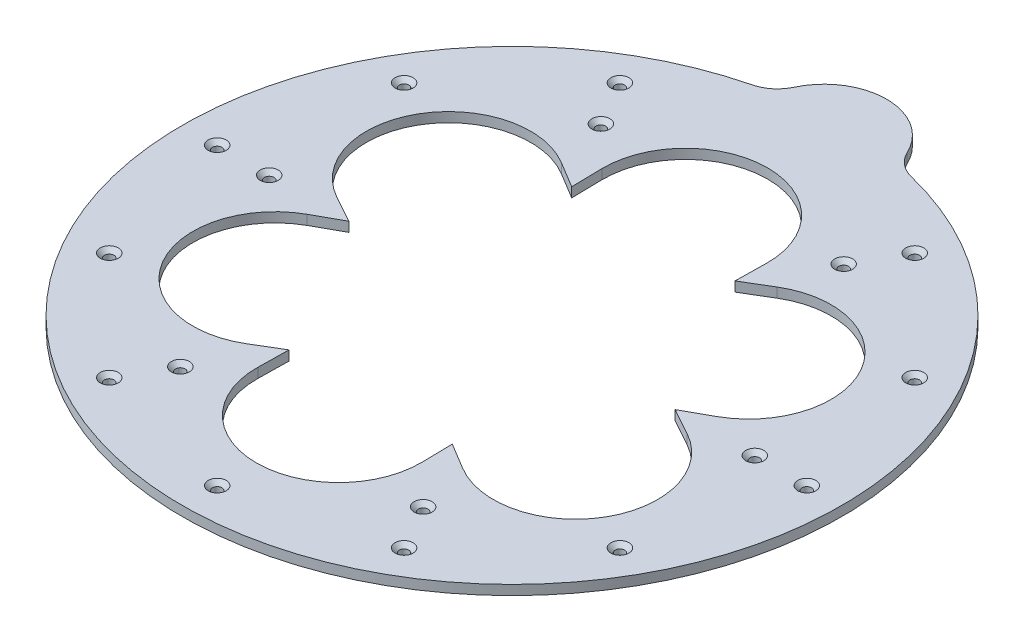
SolidWorks part; units mm, degrees
ref_plane "Front Plane" through (0, 0, 0) normal (0, 0, 1) x (1, 0, 0)
ref_plane "Top Plane" through (0, 0, 0) normal (0, 1, 0) x (1, 0, 0)
ref_plane "Right Plane" through (0, 0, 0) normal (1, 0, 0) x (0, 0, -1)
sketch "Sketch5" plane through (0, 0, 0) normal (0, 1, 0) x (1, 0, 0)
  line L25 (-47.3671, -99.136) -> (-47.0452, -81.4846)
  line L26 (47.0452, -81.4846) -> (47.3671, -99.136)
  line L28 (-47.0452, -81.4846) -> (-62.1707, -90.5891)
  line L31 (-109.5379, -8.5469) -> (-94.0903, 0)
  line L32 (-94.0903, 0) -> (-109.5379, 8.5469)
  line L35 (-62.1707, 90.5891) -> (-47.0452, 81.4846)
  line L36 (-47.0452, 81.4846) -> (-47.3671, 99.136)
  line L39 (47.3671, 99.136) -> (47.0452, 81.4846)
  line L40 (47.0452, 81.4846) -> (62.1707, 90.5891)
  line L43 (109.5379, 8.5469) -> (94.0903, 0)
  line L44 (94.0903, 0) -> (109.5379, -8.5469)
  line L47 (62.1707, -90.5891) -> (47.0452, -81.4846)
  circle A0 centre (0, 0) radius 47.9176 construction
  arc A6 (-45.8766, 184.3783) -> (45.8567, 184.3832) centre (0, 0) ccw
  circle A7 centre (0, 0) radius 29.9227 construction
  arc A14 (32.5786, 195.2947) -> (-32.5996, 195.2912) centre (-0.0097, 180) ccw
  arc A15 (-32.5996, 195.2912) -> (-45.8766, 184.3783) centre (-50.7057, 203.7865) cw
  arc A16 (32.5786, 195.2947) -> (45.8567, 184.3832) centre (50.6837, 203.792) ccw
  arc A19 (-47.3671, -99.136) -> (47.3671, -99.136) centre (0, -100) ccw
  arc A20 (-109.5379, -8.5469) -> (-62.1707, -90.5891) centre (-86.6025, -50) ccw
  arc A22 (-62.1707, 90.5891) -> (-109.5379, 8.5469) centre (-86.6025, 50) ccw
  arc A24 (47.3671, 99.136) -> (-47.3671, 99.136) centre (0, 100) ccw
  arc A26 (109.5379, 8.5469) -> (62.1707, 90.5891) centre (86.6025, 50) ccw
  arc A28 (62.1707, -90.5891) -> (109.5379, -8.5469) centre (86.6025, -50) ccw
  point P1 (0, 0)
  point P2 (0, 0)
  point P8 (0, 0)
  point P10 (0, 0)
  point P39 (-255.3022, 150.011)
  point P40 (139.5, 300)
  point P41 (0, 300)
  point P42 (-124.8076, 150)
  point P43 (-120.3076, 150)
  point P45 (-259.8076, 150)
  point P46 (135, 300)
  point P51 (0, 300)
  point P74 (0, 0)
  point P121 (0, 0)
  dimension "D2" = 20
sketch "Sketch6" plane through (0, 0, 68.1456) normal (0, -1, 0) x (1, 0, 0)
  line L0 (0, -68.1456) -> (-154.7306, -68.1456)
  circle A0 centre (0, -68.1456) radius 32.7528 construction
  circle A1 centre (0, -68.1456) radius 203.9043 construction
extrude "Boss-Extrude3" add sketch "Sketch5" against normal blind 5.6
hole_wizard "CSK for M5 Flat Head Machine Screw1" positions "Sketch8" profile "Sketch7" countersink size "M5" standard "ANSI Metric" end condition through all
sketch "Sketch8" plane through (0, 0, 68.1456) normal (0, -1, 0) x (1, 0, 0)
  line L0 (0, -68.1456) -> (-154.7306, -68.1456) construction
  point P0 (-170, -68.1456)
  dimension "D1" = 0
  dimension "D2" = 170
sketch "Sketch7" plane through (-170, 0, 0) normal (1, 0, 0) x (0, 0, 1)
  line L0 (0, 0) -> (0, 5.6)
  line L1 (0, 5.6) -> (2.75, 5.6)
  line L2 (2.75, 5.6) -> (2.75, 2.45)
  line L3 (2.75, 2.45) -> (5.2, 0)
  line L5 (5.2, 0) -> (0, 0)
  line L6 (-2.75, 2.45) -> (-5.2, 0) construction
  line L11 (0, -6.35) -> (0, 107.95) construction
  dimension "Thru Hole Dia." = 5.5
  dimension "Thru Hole Depth" = 5.6
  dimension "Near C'Sink Dia." = 10.4
  dimension "Near C'Sink Angle" = 90
pattern_circular "CirPattern1" count 12 every 30 about axis through (0, -5.6, 0) along (0, 1, 0) skipping 9 of "CSK for M5 Flat Head Machine Screw1"
hole_wizard "CSK for M5 Flat Head Machine Screw2" positions "Sketch10" profile "Sketch9" countersink size "M5" standard "ANSI Metric" end condition through all
sketch "Sketch10" plane through (0, 0, 68.1456) normal (0, -1, 0) x (1, 0, 0)
  line L0 (0, -68.1456) -> (-154.7306, -68.1456) construction
  point P0 (-140, -68.1456)
  dimension "D1" = 0
  dimension "D2" = 140
sketch "Sketch9" plane through (-140, 0, 0) normal (1, 0, 0) x (0, 0, 1)
  line L0 (0, 0) -> (0, 5.6)
  line L1 (0, 5.6) -> (2.75, 5.6)
  line L2 (2.75, 5.6) -> (2.75, 2.45)
  line L3 (2.75, 2.45) -> (5.2, 0)
  line L5 (5.2, 0) -> (0, 0)
  line L6 (-2.75, 2.45) -> (-5.2, 0) construction
  line L11 (0, -6.35) -> (0, 107.95) construction
  dimension "Thru Hole Dia." = 5.5
  dimension "Thru Hole Depth" = 5.6
  dimension "Near C'Sink Dia." = 10.4
  dimension "Near C'Sink Angle" = 90
pattern_circular "CirPattern2" count 6 over 360 about axis through (0, -5.6, 0) along (0, 1, 0) of "CSK for M5 Flat Head Machine Screw2"
ref_plane "Plane1" [suppressed] through (0, 0, 0) normal (0, 1, 0) x (1, 0, 0)
sketch "Sketch11" [suppressed] plane through (0, 0, 0) normal (0, 1, 0) x (1, 0, 0)
  circle A0 centre (-0.0097, 180) radius 6.35
extrude "Cut-Extrude1" [suppressed] cut sketch "Sketch11" against normal blind 10
sketch "keepThisTemplate" plane through (0, 0, 0) normal (0, 1, 0) x (1, 0, 0)
  line L0 (-86.6025, -4.4286) -> (-67.2981, -15.1094)
  line L1 (-47.1365, -72.7857) -> (-46.7342, -50.7272)
  line L2 (-47.1365, -72.7857) -> (-66.0386, -84.1634)
  line L3 (-105.9069, -15.1094) -> (-86.6025, -4.4286)
  line L4 (-47.1365, 72.7857) -> (-46.7342, 50.7272)
  line L5 (-86.6025, 4.4286) -> (-67.2981, 15.1094)
  line L6 (-86.6025, 4.4286) -> (-105.9069, 15.1094)
  line L7 (-66.0386, 84.1634) -> (-47.1365, 72.7857)
  line L8 (-39.466, -77.2143) -> (-20.564, -65.8366)
  line L9 (39.466, -77.2143) -> (20.564, -65.8366)
  line L10 (39.466, -77.2143) -> (39.8684, -99.2728)
  line L11 (-39.8684, -99.2728) -> (-39.466, -77.2143)
  line L12 (39.466, 77.2143) -> (20.564, 65.8366)
  line L13 (-39.466, 77.2143) -> (-20.564, 65.8366)
  line L14 (-39.466, 77.2143) -> (-39.8684, 99.2728)
  line L15 (39.8684, 99.2728) -> (39.466, 77.2143)
  line L16 (86.6025, 4.4286) -> (67.2981, 15.1094)
  line L17 (47.1365, 72.7857) -> (46.7342, 50.7272)
  line L18 (47.1365, 72.7857) -> (66.0386, 84.1634)
  line L19 (105.9069, 15.1094) -> (86.6025, 4.4286)
  line L20 (47.1365, -72.7857) -> (46.7342, -50.7272)
  line L21 (86.6025, -4.4286) -> (67.2981, -15.1094)
  line L22 (86.6025, -4.4286) -> (105.9069, -15.1094)
  line L23 (66.0386, -84.1634) -> (47.1365, -72.7857)
  line L24 (-46.8891, -72.9286) -> (-24.4318, -59.4109)
  line L25 (-47.3671, -99.136) -> (-46.8891, -72.9286)
  line L26 (46.8891, -72.9286) -> (47.3671, -99.136)
  line L27 (46.8891, -72.9286) -> (24.4318, -59.4109)
  line L28 (-39.7135, -77.0714) -> (-62.1707, -90.5891)
  line L29 (-39.7135, -77.0714) -> (-39.2354, -50.864)
  line L30 (-86.6025, 4.1429) -> (-63.6672, -8.5469)
  line L31 (-109.5379, -8.5469) -> (-86.6025, 4.1429)
  line L32 (-86.6025, -4.1429) -> (-109.5379, 8.5469)
  line L33 (-86.6025, -4.1429) -> (-63.6672, 8.5469)
  line L34 (-39.7135, 77.0714) -> (-39.2354, 50.864)
  line L35 (-62.1707, 90.5891) -> (-39.7135, 77.0714)
  line L36 (-46.8891, 72.9286) -> (-47.3671, 99.136)
  line L37 (-46.8891, 72.9286) -> (-24.4318, 59.4109)
  line L38 (46.8891, 72.9286) -> (24.4318, 59.4109)
  line L39 (47.3671, 99.136) -> (46.8891, 72.9286)
  line L40 (39.7135, 77.0714) -> (62.1707, 90.5891)
  line L41 (39.7135, 77.0714) -> (39.2354, 50.864)
  line L42 (86.6025, -4.1429) -> (63.6672, 8.5469)
  line L43 (109.5379, 8.5469) -> (86.6025, -4.1429)
  line L44 (86.6025, 4.1429) -> (109.5379, -8.5469)
  line L45 (86.6025, 4.1429) -> (63.6672, -8.5469)
  line L46 (39.7135, -77.0714) -> (39.2354, -50.864)
  line L47 (62.1707, -90.5891) -> (39.7135, -77.0714)
  circle A0 centre (0, 0) radius 47.9176 construction
  arc A1 (-46.7342, -50.7272) -> (-67.2981, -15.1094) centre (-86.6025, -50) ccw
  arc A2 (-105.9069, -15.1094) -> (-66.0386, -84.1634) centre (-86.6025, -50) ccw
  arc A3 (-67.2981, 15.1094) -> (-46.7342, 50.7272) centre (-86.6025, 50) ccw
  arc A4 (20.564, -65.8366) -> (-20.564, -65.8366) centre (0, -100) ccw
  arc A5 (-66.0386, 84.1634) -> (-105.9069, 15.1094) centre (-86.6025, 50) ccw
  arc A6 (-39.8684, -99.2728) -> (39.8684, -99.2728) centre (0, -100) ccw
  arc A7 (-20.564, 65.8366) -> (20.564, 65.8366) centre (0, 100) ccw
  arc A8 (39.8684, 99.2728) -> (-39.8684, 99.2728) centre (0, 100) ccw
  arc A9 (46.7342, 50.7272) -> (67.2981, 15.1094) centre (86.6025, 50) ccw
  arc A10 (105.9069, 15.1094) -> (66.0386, 84.1634) centre (86.6025, 50) ccw
  arc A11 (67.2981, -15.1094) -> (46.7342, -50.7272) centre (86.6025, -50) ccw
  arc A12 (66.0386, -84.1634) -> (105.9069, -15.1094) centre (86.6025, -50) ccw
  arc A13 (24.4318, -59.4109) -> (-24.4318, -59.4109) centre (0, -100) ccw
  arc A14 (-47.3671, -99.136) -> (47.3671, -99.136) centre (0, -100) ccw
  arc A15 (-109.5379, -8.5469) -> (-62.1707, -90.5891) centre (-86.6025, -50) ccw
  arc A16 (-39.2354, -50.864) -> (-63.6672, -8.5469) centre (-86.6025, -50) ccw
  arc A17 (-62.1707, 90.5891) -> (-109.5379, 8.5469) centre (-86.6025, 50) ccw
  arc A18 (-63.6672, 8.5469) -> (-39.2354, 50.864) centre (-86.6025, 50) ccw
  arc A19 (47.3671, 99.136) -> (-47.3671, 99.136) centre (0, 100) ccw
  arc A20 (-24.4318, 59.4109) -> (24.4318, 59.4109) centre (0, 100) ccw
  arc A21 (109.5379, 8.5469) -> (62.1707, 90.5891) centre (86.6025, 50) ccw
  arc A22 (39.2354, 50.864) -> (63.6672, 8.5469) centre (86.6025, 50) ccw
  arc A23 (62.1707, -90.5891) -> (109.5379, -8.5469) centre (86.6025, -50) ccw
  arc A24 (63.6672, -8.5469) -> (39.2354, -50.864) centre (86.6025, -50) ccw
  point P39 (-42.5504, 25.0018)
  point P40 (23.25, 50)
  point P41 (0, 50)
  point P42 (-20.8013, 25)
  point P43 (-20.0513, 25)
  point P45 (-43.3013, 25)
  point P46 (22.5, 50)
  point P51 (0, 50)
  point P61 (0, 0)
  point P110 (0, 0)
  dimension "D1" = 6
  dimension "D2" = 7.5
  dimension "D3" = 6
